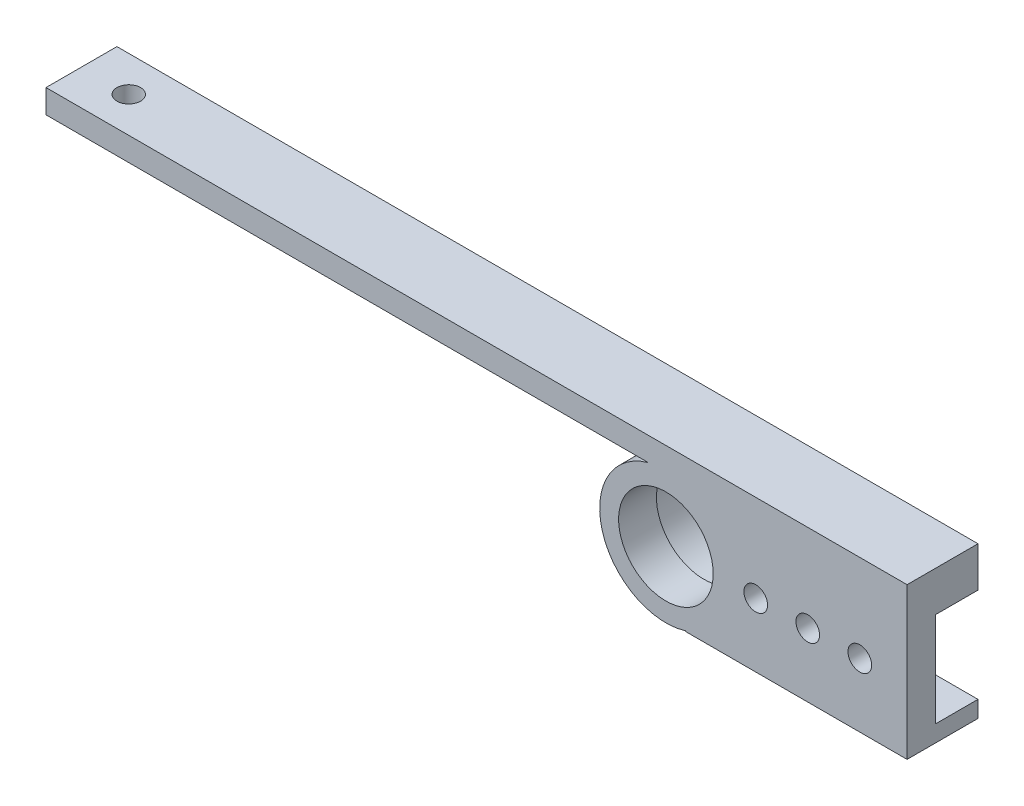
SolidWorks part; units mm, degrees
ref_plane "前视基准面" through (0, 0, 0) normal (0, 0, 1) x (1, 0, 0)
ref_plane "上视基准面" through (0, 0, 0) normal (0, 1, 0) x (1, 0, 0)
ref_plane "右视基准面" through (0, 0, 0) normal (1, 0, 0) x (0, 0, -1)
sketch "草图1" plane through (0, 0, 0) normal (0, 0, 1) x (1, 0, 0)
  line L1 (20, -10) -> (-20, -10)
  line L2 (20, -10) -> (20, 10)
  line L3 (20, 10) -> (-20, 10)
  line L4 (-20, -10) -> (-20, 10)
  line L5 (20, -10) -> (-20, 10) construction
  line L6 (20, 10) -> (-20, -10) construction
  point P0 (0, 0)
  dimension "D1" = 40
  dimension "D2" = 20
extrude "凸台-拉伸1" add sketch "草图1" along normal blind 6
sketch "草图2" plane through (0, 0, 6) normal (0, 0, 1) x (1, 0, 0)
  line L0 (20, -10) -> (20, 10) construction
  circle A0 centre (10, 0) radius 2.5
  circle A1 centre (-1, 0) radius 2.5
  circle A2 centre (-12, 0) radius 2.5
  dimension "D1" = 10
  dimension "D2" = 5
  dimension "D3" = 3
extrude "切除-拉伸1" cut sketch "草图2" against normal through all
sketch "草图3" plane through (0, 0, 6) normal (0, 0, 1) x (1, 0, 0)
  line L0 (20, 13.5) -> (20, 10)
  line L1 (20, -13.5) -> (-26.894, -13.5)
  line L3 (20, 13.5) -> (-26.894, 13.5)
  line L4 (-20, 10) -> (-20, -10)
  line L5 (-20, -10) -> (20, -10)
  line L6 (20, -10) -> (20, 10)
  line L7 (20, 10) -> (-20, 10)
  line L8 (-20, 10) -> (-20, -10)
  line L9 (-20, -10) -> (20, -10)
  line L10 (20, -10) -> (20, 10)
  line L11 (20, 10) -> (-20, 10)
  line L12 (-26.894, -13.5) -> (-26.894, 13.5)
  line L13 (20, -10.0394) -> (-26.894, 13.5) construction
  line L14 (20, 10.0394) -> (-26.894, -13.5) construction
  line L15 (20, -10) -> (20, -13.5)
  circle A0 centre (-31, 0) radius 11
  circle A1 centre (-31, 0) radius 14
  point P2 (0, 0)
  line M10 (-20, 10) -> (-20, -10)
  line M11 (-20, -10) -> (20, -10)
  line M13 (20, 10) -> (-20, 10)
  dimension "D3" = 22
  dimension "D4" = 28
  dimension "D2" = 3.5
  dimension "D1" = 0
extrude "凸台-拉伸2" add sketch "草图3" against normal blind 15 contours L3 A1 L1 L12 A0 | A1 L1 L15 M11 M10 | L1 A1 L8 A0 L12 | L8 A1 L3 L12 A0 | L8 A1 | A1 L0 L3 M10 M13 region at (-1.9449, 11.7771, 6) region at (-1.9449, -11.7771, 6) region at (-23.0173, 9.0328, 6) region at (-27.2274, 11.7946, 6) region at (-18.7882, 0, 6) region at (-23.0173, -9.0328, 6)
sketch "草图5" plane through (0, 0, 6) normal (0, 0, 1) x (1, 0, 0)
  circle A0 centre (-31, 0) radius 10
  circle A1 centre (-31, 0) radius 11 construction
  circle A2 centre (-31, 0) radius 11
  dimension "D1" = 20
extrude "凸台-拉伸3" add sketch "草图5" against normal blind 8
sketch "草图6" plane through (0, 0, 6) normal (0, 0, 1) x (1, 0, 0)
  circle A0 centre (-31, 0) radius 8.5
  circle A1 centre (-31, 0) radius 10 construction
  circle A2 centre (-31, 0) radius 10
  dimension "D1" = 17
sketch "草图7" plane through (0, 13.5, 0) normal (0, 1, 0) x (1, 0, 0)
  circle A0 centre (-16.8213, 3.0525) radius 3.3366
sketch "草图8" plane through (20, 0, 0) normal (1, 0, 0) x (0, 0, -1)
  line L1 (-6, 13.5) -> (9, 13.5)
  line L2 (-6, 13.5) -> (-6, 18.5)
  line L3 (-6, 18.5) -> (9, 18.5)
  line L4 (9, 13.5) -> (9, 18.5)
  dimension "D1" = 5
extrude "凸台-拉伸4" add sketch "草图8" against normal blind 200
sketch "草图9" plane through (0, 0, 6) normal (0, 0, 1) x (1, 0, 0)
  line L1 (-29.5663, 15.6648) -> (-25.1627, 15.6648)
  line L2 (-29.5663, 15.6648) -> (-29.5663, 11.9284)
  line L3 (-29.5663, 11.9284) -> (-25.1627, 11.9284)
  line L4 (-25.1627, 15.6648) -> (-25.1627, 11.9284)
extrude "凸台-拉伸5" add sketch "草图9" against normal through all
sketch "草图11" plane through (0, 18.5, 0) normal (0, 1, 0) x (1, 0, 0)
  line L0 (-118.4338, -6) -> (-118.4338, 9)
  line L1 (-180, -6) -> (20, -6) construction
  line L2 (-118.4338, 246.7017) -> (-118.4338, -123.2983) construction
  line L3 (-180, 9) -> (20, 9) construction
sketch "草图13" plane through (0, 18.5, 0) normal (0, 1, 0) x (1, 0, 0)
  line L1 (-118.4338, -6) -> (-183.1111, -6)
  line L2 (-118.4338, -6) -> (-118.4338, 12.5245)
  line L3 (-118.4338, 12.5245) -> (-183.1111, 12.5245)
  line L4 (-183.1111, -6) -> (-183.1111, 12.5245)
extrude "切除-拉伸2" cut sketch "草图13" against normal through all
sketch "草图14" plane through (0, 18.5, 0) normal (0, 1, 0) x (1, 0, 0)
  line L0 (-162.0913, 11.0465) -> (-162.0913, -39.4434)
  line L1 (-162.0913, 244.91) -> (-162.0913, -125.09) construction
sketch "草图15" plane through (0, 18.5, 0) normal (0, 1, 0) x (1, 0, 0)
  line L0 (-162.0913, 11.0465) -> (-162.0913, -39.4434) construction
  line L1 (-118.4338, -6) -> (-162.0913, -6)
  line L2 (-118.4338, -6) -> (-118.4338, 9)
  line L3 (-118.4338, 9) -> (-162.0913, 9)
  line L4 (-162.0913, -6) -> (-162.0913, 9)
extrude "凸台-拉伸6" add sketch "草图15" against normal blind 5
sketch "草图16" plane through (0, 18.5, 0) normal (0, 1, 0) x (1, 0, 0)
  line L0 (-162.0913, 9) -> (-162.0913, -6)
  line L1 (-162.0913, 1.5) -> (-152.0913, 1.5) construction
  circle A0 centre (-152.0913, 1.5) radius 2.5
  dimension "D1" = 5
  dimension "D2" = 10
extrude "切除-拉伸3" cut sketch "草图16" against normal through all contours A0 region at (-152.0913, 18.5, -1.5)
